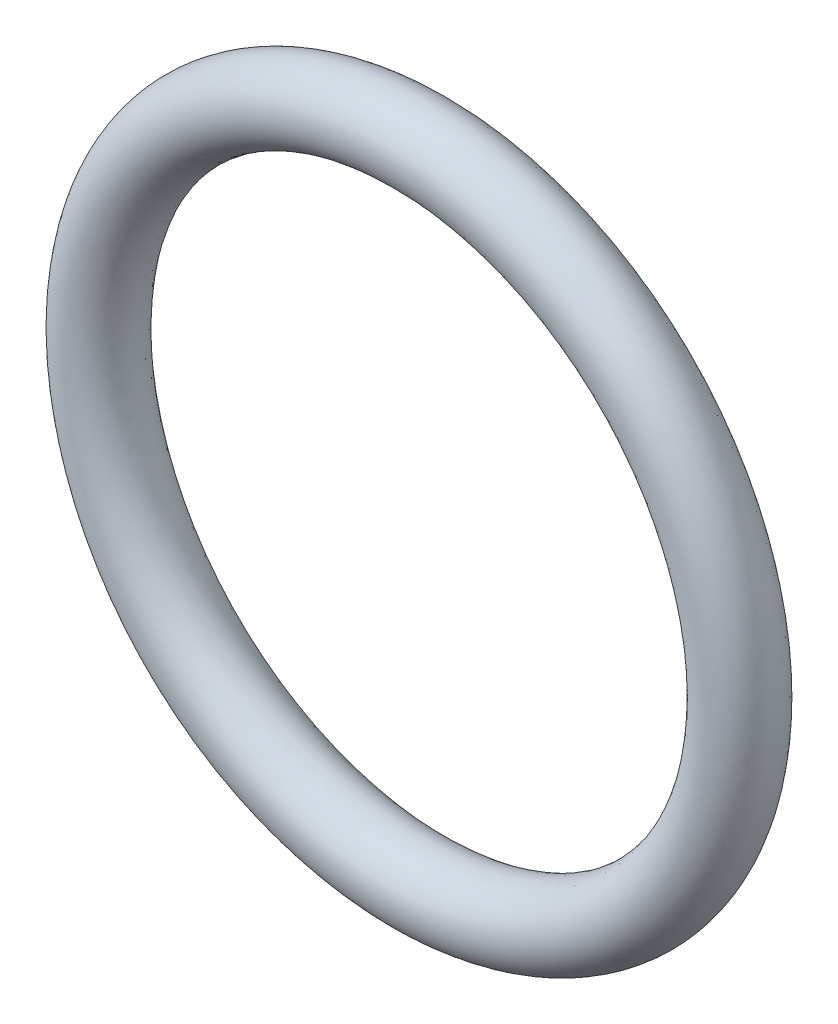
SolidWorks part; units mm, degrees
material "Caoutchouc silicone"
ref_plane "Plan1" through (0, 0, 0) normal (0, 0, 1) x (1, 0, 0)
ref_plane "Plan2" through (0, 0, 0) normal (0, 1, 0) x (1, 0, 0)
ref_plane "Plan3" through (0, 0, 0) normal (1, 0, 0) x (0, 0, -1)
sketch "Esquisse1" plane through (0, 0, 0) normal (1, 0, 0) x (0, 0, -1)
  line L0 (0, 0) -> (5.32, 0) construction
  ellipse E0 centre (2.66, 22.98) end of major axis (5.32, 22.98) minor radius 2.66
  dimension "Di" = 20.32
revolve "Base-Révolution" add sketch "Esquisse1" angle 360 about L0
ref_axis "Axe1" through (0, 0, -50) along (0, 0, 1)
ref_plane "Plan4" through (0, 0, -2.66) normal (0, 0, 1) x (1, 0, 0)
